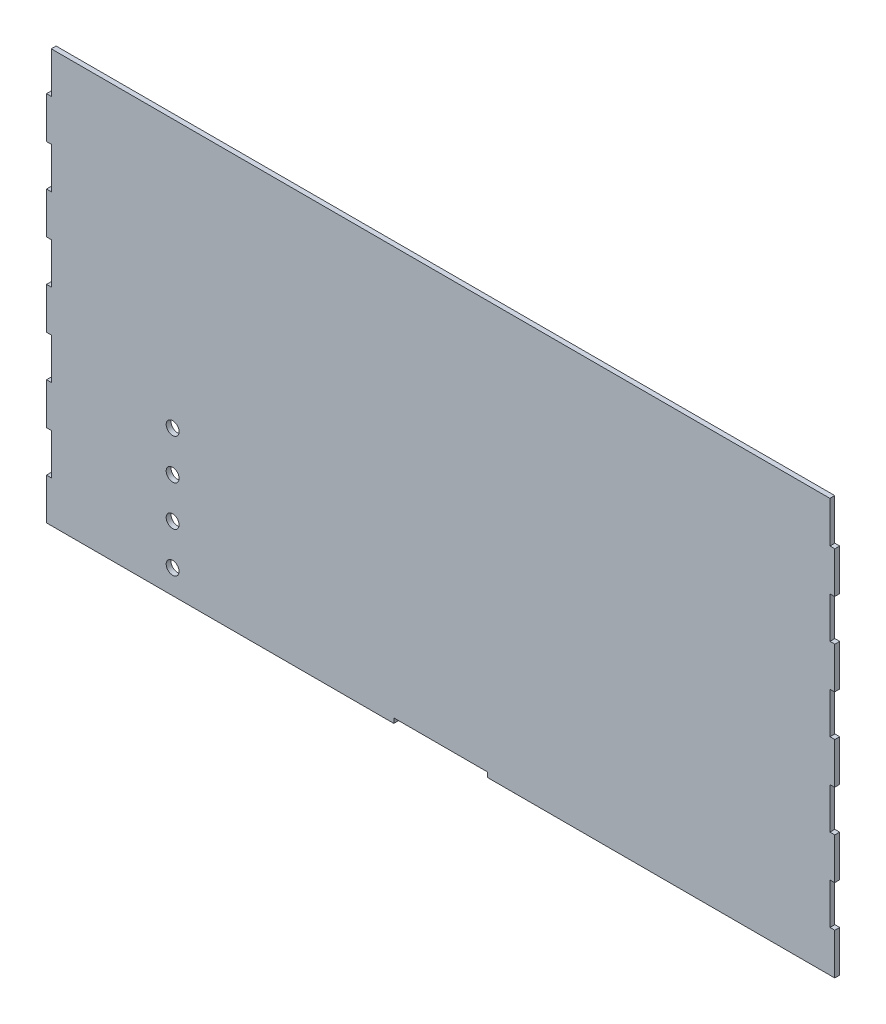
SolidWorks part; units mm, degrees
material "Pine"
ref_plane "Front Plane" through (0, 0, 0) normal (0, 0, 1) x (1, 0, 0)
ref_plane "Top Plane" through (0, 0, 0) normal (0, 1, 0) x (1, 0, 0)
ref_plane "Right Plane" through (0, 0, 0) normal (1, 0, 0) x (0, 0, -1)
sketch "Sketch1" plane through (0, 0, 0) normal (0, 0, 1) x (1, 0, 0)
  line L1 (-488.6875, 256) -> (488.6875, 256)
  line L2 (-488.6875, 256) -> (-488.6875, -256)
  line L3 (-488.6875, -256) -> (488.6875, -256)
  line L4 (488.6875, 256) -> (488.6875, -256)
  line L5 (-488.6875, 256) -> (488.6875, -256) construction
  line L6 (-488.6875, -256) -> (488.6875, 256) construction
  point P4 (0, 0)
  dimension "D1" = 977.375
  dimension "D2" = 512
  dimension "D3" = 0
  dimension "D4" = 0
extrude "Boss-Extrude1" add sketch "Sketch1" along normal blind 6
sketch "Sketch7" plane through (0, 0, 6) normal (0, 0, 1) x (1, 0, 0)
  line L0 (488.6875, -256) -> (488.6875, 256) construction
  line L1 (488.6875, -204.8) -> (482.6875, -204.8)
  line L2 (488.6875, -204.8) -> (488.6875, -153.6)
  line L3 (488.6875, -153.6) -> (482.6875, -153.6)
  line L4 (482.6875, -204.8) -> (482.6875, -153.6)
  line L5 (-488.6875, -256) -> (488.6875, -256) construction
  ellipse E0 centre (485.6875, -204.8) end of major axis (488.6875, -204.8) minor radius 0.2
  ellipse E1 centre (485.6875, -153.6) end of major axis (488.6875, -153.6) minor radius 0.2
  line M8 (488.6875, -256) -> (488.6875, 256)
  dimension "D1" = 6
  dimension "D2" = 51.2
  dimension "D3" = 51.2
  dimension "D4" = 0.2
  dimension "D5" = 0.2
extrude "Cut-Extrude3" cut sketch "Sketch7" against normal blind 10 contours E0 L3 L4 M8 region at (485.6875, -179.2, 6)
pattern_linear "LPattern1" count 5 spacing 102.4 along (0, 1, 0) of "Cut-Extrude3"
sketch "Sketch8" plane through (0, 0, 6) normal (0, 0, 1) x (1, 0, 0)
  line L1 (482.6875, 256) -> (488.6875, 256)
  line L2 (482.6875, 256) -> (482.6875, 255.4193)
  line L3 (482.6875, 255.4193) -> (488.6875, 255.4193)
  line L4 (488.6875, 256) -> (488.6875, 255.4193)
  dimension "D1" = 6
  dimension "D2" = 0.5807
extrude "Cut-Extrude4" cut sketch "Sketch8" against normal blind 10
sketch "Sketch10" plane through (0, 0, 6) normal (0, 0, 1) x (1, 0, 0)
  line L0 (-488.6875, 256) -> (-488.6875, -256) construction
  line L1 (-488.6875, -204.8) -> (-482.6875, -204.8)
  line L2 (-488.6875, -204.8) -> (-488.6875, -153.6)
  line L3 (-488.6875, -153.6) -> (-482.6875, -153.6)
  line L4 (-482.6875, -204.8) -> (-482.6875, -153.6)
  line L5 (-488.6875, -256) -> (488.6875, -256) construction
  ellipse E0 centre (-485.6875, -204.8) end of major axis (-482.6875, -204.8) minor radius 0.2
  ellipse E1 centre (-485.6875, -153.6) end of major axis (-482.6875, -153.6) minor radius 0.2
  line M18 (-488.6875, 256) -> (-488.6875, -256)
  dimension "D1" = 6
  dimension "D2" = 102.4
  dimension "D3" = 51.2
  dimension "D4" = 0.2
  dimension "D5" = 0.2
extrude "Cut-Extrude5" cut sketch "Sketch10" against normal blind 10 contours E1 E0 L4 M18 region at (-485.6875, -179.2, 6)
pattern_linear "LPattern4" count 5 spacing 102.4 along (0, 1, 0) of "Cut-Extrude5"
sketch "Sketch11" plane through (0, 0, 6) normal (0, 0, 1) x (1, 0, 0)
  line L1 (-482.6875, 256) -> (-488.6875, 256)
  line L2 (-482.6875, 256) -> (-482.6875, 255.2668)
  line L3 (-482.6875, 255.2668) -> (-488.6875, 255.2668)
  line L4 (-488.6875, 256) -> (-488.6875, 255.2668)
  dimension "D1" = 6
  dimension "D2" = 0.7332
extrude "Cut-Extrude6" cut sketch "Sketch11" against normal blind 10 contours L3 L4 L1 L2
sketch "Sketch12" plane through (0, 0, 6) normal (0, 0, 1) x (1, 0, 0)
  line L0 (282.1875, 256) -> (282.1875, -256)
  line L1 (482.6875, 256) -> (-482.6875, 256) construction
  line L2 (-488.6875, -256) -> (488.6875, -256) construction
  line L3 (488.6875, 153.6) -> (488.6875, 204.8) construction
  line L4 (-282.1875, 256) -> (-282.1875, -256)
  line L5 (-488.6875, 204.8) -> (-488.6875, 153.6) construction
  line L6 (-206, 256) -> (-206, -256)
  dimension "D1" = 206.5
  dimension "D2" = 206.5
  dimension "D3" = 206
sketch "Sketch13" plane through (0, 0, 6) normal (0, 0, 1) x (1, 0, 0)
  line L0 (206, 256) -> (206, -256)
  line L1 (482.6875, 256) -> (-482.6875, 256) construction
  line L2 (-488.6875, -256) -> (488.6875, -256) construction
  dimension "D1" = 206
sketch "Sketch14" plane through (0, 0, 6) normal (0, 0, 1) x (1, 0, 0)
  line L1 (-58, -250.0304) -> (58, -250.0304)
  line L2 (-58, -250.0304) -> (-58, -256.0304)
  line L3 (-58, -256.0304) -> (58, -256.0304)
  line L4 (58, -250.0304) -> (58, -256.0304)
  line L5 (-58, -250.0304) -> (58, -256.0304) construction
  line L6 (-58, -256.0304) -> (58, -250.0304) construction
  point P4 (0, -253.0304)
  dimension "D1" = 148
  dimension "D2" = 148
extrude "Cut-Extrude9" cut sketch "Sketch14" against normal blind 10 contours L2 L1 L4 L3
sketch "Sketch15" plane through (0, 0, 6) normal (0, 0, 1) x (1, 0, 0)
  line L0 (-488.6875, -256) -> (-58, -256) construction
  line L1 (-282.1875, 256) -> (-282.1875, -256) construction
  circle A0 centre (-332.1875, -226) radius 8
  dimension "D1" = 30
  dimension "D2" = 50
extrude "Cut-Extrude11" cut sketch "Sketch15" against normal blind 10
pattern_linear "LPattern5" count 4 spacing 50 along (0, 1, 0) of "Cut-Extrude11"
